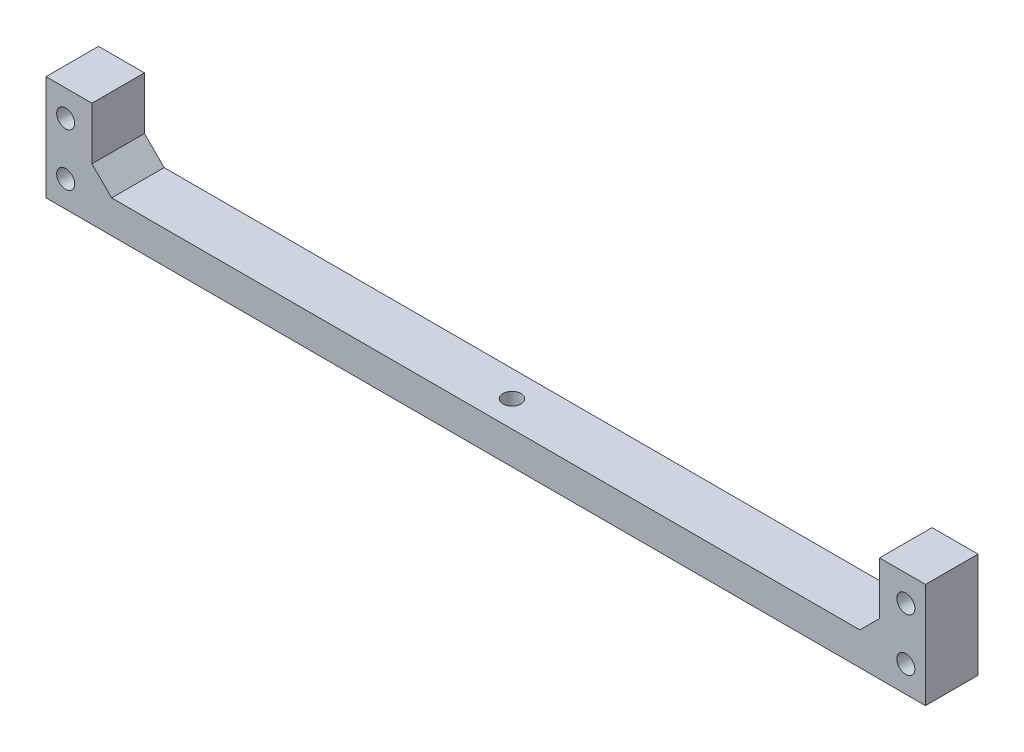
SolidWorks part; units mm, degrees
ref_plane "Front Plane" through (0, 0, 0) normal (0, 0, 1) x (1, 0, 0)
ref_plane "Top Plane" through (0, 0, 0) normal (0, 1, 0) x (1, 0, 0)
ref_plane "Right Plane" through (0, 0, 0) normal (1, 0, 0) x (0, 0, -1)
sketch "Sketch1" plane through (0, 0, 0) normal (0, 1, 0) x (1, 0, 0)
  line L0 (-107.95, 0) -> (107.95, 0)
  line L6 (107.95, 12.7) -> (-107.95, 12.7)
  line L12 (107.95, 0) -> (107.95, 12.7)
  line L13 (-107.95, 0) -> (-107.95, 12.7)
  point P4 (0, 0)
  dimension "D1" = 215.9
  dimension "D2" = 12.7
extrude "Boss-Extrude1" add sketch "Sketch1" along normal mid plane 12.7
sketch "Sketch3" plane through (0, 0, 0) normal (0, 0, 1) x (1, 0, 0)
  line L0 (-95.25, 6.35) -> (-90.4875, 1.5875)
  line L1 (-107.95, 6.35) -> (107.95, 6.35) construction
  line L2 (-90.4875, 1.5875) -> (90.4875, 1.5875)
  line L3 (90.4875, 1.5875) -> (95.25, 6.35)
  line L6 (-95.25, 6.35) -> (95.25, 6.35)
  line L7 (107.95, 6.35) -> (107.95, -6.35) construction
  line L8 (-107.95, 6.35) -> (-107.95, -6.35) construction
  dimension "D1" = 12.7
  dimension "D2" = 12.7
  dimension "D3" = 4.7625
  dimension "D4" = 45
  dimension "D5" = 45
extrude "Cut-Extrude2" cut sketch "Sketch3" against normal through all both and the other way through all
sketch "Sketch4" plane through (0, -6.35, 0) normal (0, -1, 0) x (1, 0, 0)
  line L0 (90.4875, 0) -> (-90.4875, 0) construction
  circle A1 centre (0, -6.35) radius 2.1828
  dimension "D5" = 4.3656
  dimension "D1" = 6.35
extrude "Cut-Extrude3" cut sketch "Sketch4" against normal through all both and the other way through all
sketch "Sketch5" plane through (0, 6.35, 0) normal (0, 1, 0) x (1, 0, 0)
  line L1 (-107.95, 12.7) -> (-95.25, 12.7)
  line L2 (-107.95, 12.7) -> (-107.95, 0)
  line L3 (-107.95, 0) -> (-95.25, 0)
  line L4 (-95.25, 12.7) -> (-95.25, 0)
  line L5 (107.95, 0) -> (95.25, 0)
  line L6 (107.95, 0) -> (107.95, 12.7)
  line L7 (107.95, 12.7) -> (95.25, 12.7)
  line L8 (95.25, 0) -> (95.25, 12.7)
extrude "Boss-Extrude2" add sketch "Sketch5" along normal blind 12.7
sketch "Sketch2" plane through (0, 0, 0) normal (0, 0, 1) x (1, 0, 0)
  line L0 (-107.95, -6.35) -> (107.95, -6.35) construction
  line L1 (107.95, 19.05) -> (106.3625, 19.05)
  line L2 (-107.95, 19.05) -> (-107.95, -6.35) construction
  line L3 (107.95, 19.05) -> (107.95, -6.35) construction
  line L4 (107.95, 19.05) -> (107.95, -6.35)
  line L5 (107.95, -6.35) -> (106.3625, -6.35)
  line L6 (106.3625, 19.05) -> (106.3625, -6.35)
  line L8 (-107.95, 19.05) -> (-106.3625, 19.05)
  line L9 (-107.95, 19.05) -> (-107.95, -6.35)
  line L10 (-107.95, -6.35) -> (-106.3625, -6.35)
  line L11 (-106.3625, 19.05) -> (-106.3625, -6.35)
  circle A0 centre (-101.6, 0) radius 2.1828
  circle A2 centre (101.6, 0) radius 2.1828
  circle A4 centre (-101.6, 12.7) radius 2.1828
  circle A5 centre (101.6, 12.7) radius 2.1828
  dimension "D5" = 4.3656
  dimension "D6" = 4.3656
  dimension "D7" = 4.3656
  dimension "D8" = 1.5875
  dimension "D4" = 4.3656
  dimension "D1" = 6.35
  dimension "D2" = 12.7
  dimension "D3" = 6.35
  dimension "D9" = 1.5875
extrude "Cut-Extrude1" cut sketch "Sketch2" against normal through all both and the other way through all
